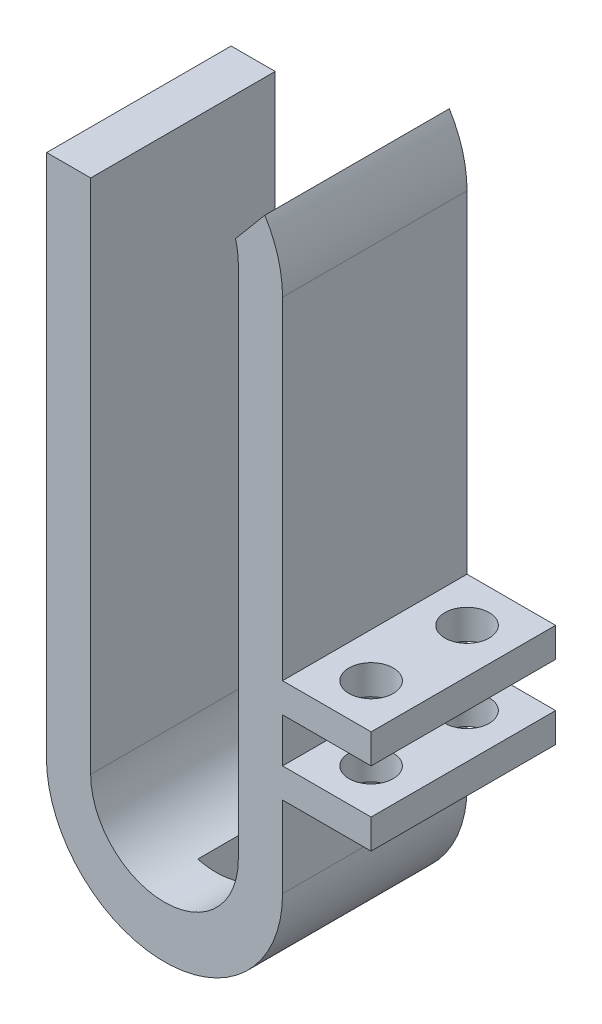
SolidWorks part; units mm, degrees
ref_plane "Front Plane" through (0, 0, 0) normal (0, 0, 1) x (1, 0, 0)
ref_plane "Top Plane" through (0, 0, 0) normal (0, 1, 0) x (1, 0, 0)
ref_plane "Right Plane" through (0, 0, 0) normal (1, 0, 0) x (0, 0, -1)
sketch "Sketch1" plane through (0, 0, 0) normal (0, 0, 1) x (1, 0, 0)
  line L0 (0, 17.5) -> (0, -17.5) construction
  line L1 (5, 17.5) -> (5, -17.5)
  line L2 (-5, 8.5) -> (-5, -17.5)
  line L3 (8, 17) -> (8, -18)
  line L4 (-8, 11.5) -> (-8, -18)
  line L6 (-8, 11.5) -> (-5, 8.5)
  line L9 (-5, 17.5) -> (-5, 8.5)
  line L10 (-8, 17) -> (-8, 11.5)
  line L11 (-6.105, 27.1604) -> (2.0351, 15.5351)
  line L12 (-5, 8.5) -> (2.0351, 15.5351)
  line L13 (-7.9844, 17.5) -> (7.9844, 17.5)
  line L14 (2.0351, 15.5351) -> (9.5686, 24.5132)
  arc A0 (5, 17.5) -> (-5, 17.5) centre (0, 17.5) ccw
  arc A1 (-5, -17.5) -> (5, -17.5) centre (0, -17.5) ccw
  arc A2 (-8, -18) -> (8, -18) centre (0, -18) ccw
  arc A3 (8, 17) -> (-8, 17) centre (0, 17) ccw
  point P2 (0, 0)
  point P15 (0, 0)
  dimension "D4" = 35
  dimension "D7" = 100
  dimension "D8" = 75
  dimension "D1" = 3
  dimension "D2" = 3
  dimension "D3" = 5
  dimension "D5" = 35
  dimension "D6" = 17
extrude "Boss-Extrude1" add sketch "Sketch1" along normal blind 12.5 contours L3 A3 A0 L1 A1 L2 L6 L4 A2 | L13 A3 L10 L6 L9 | L13 A3 L14 A0 region at (6.4922, 17.0365, 0) region at (6.4627, 18.8851, 0) region at (-6.3998, 13.6996, 0)
sketch "Sketch2" plane through (8, 0, 0) normal (1, 0, 0) x (0, 0, -1)
  line L0 (0, 17) -> (0, -18) construction
  line L7 (-12.5, 17) -> (0, 17) construction
  line L8 (-12.5, 17) -> (-12.5, -18) construction
  line L9 (-12.5, -12.5) -> (0, -12.5)
  line L10 (-12.5, -12.5) -> (-12.5, -10.5)
  line L11 (-12.5, -10.5) -> (0, -10.5)
  line L12 (0, -12.5) -> (0, -10.5)
  line L13 (-12.5, -5.5) -> (0, -5.5)
  line L14 (-12.5, -5.5) -> (-12.5, -7.5)
  line L15 (-12.5, -7.5) -> (0, -7.5)
  line L16 (0, -5.5) -> (0, -7.5)
  dimension "D1" = 22.5
  dimension "D2" = 3
  dimension "D3" = 2
  dimension "D4" = 2
extrude "Boss-Extrude2" add sketch "Sketch2" along normal blind 6
sketch "Sketch3" plane through (0, -10.5, 0) normal (0, 1, 0) x (1, 0, 0)
  line L0 (14, 0) -> (8, 0) construction
  line L1 (8, -6.25) -> (14, -6.25) construction
  line L2 (8, 0) -> (8, -12.5) construction
  line L3 (14, 0) -> (14, -12.5) construction
  circle A1 centre (11, -3) radius 1.5
  circle A2 centre (11, -9.5) radius 1.5
  point P10 (11, -9.5)
  dimension "D1" = 3
  dimension "D2" = 3
  dimension "D3" = 3
extrude "Cut-Extrude1" cut sketch "Sketch3" against normal through all both and the other way through all
sketch "Sketch5" plane through (0, 0, 0) normal (0, 1, 0) x (1, 0, 0)
  line L0 (-8, -12.5) -> (-8, 0) construction
  line L1 (-1.25, -3.5) -> (1.25, -3.5)
  line L2 (-1.25, -3.5) -> (-1.25, -9)
  line L3 (-1.25, -9) -> (1.25, -9)
  line L4 (1.25, -3.5) -> (1.25, -9)
  line L7 (5, 0) -> (-5, 0) construction
  dimension "D1" = 5.5
  dimension "D2" = 2.5
  dimension "D3" = 6.75
  dimension "D4" = 3.5
extrude "Cut-Extrude2" cut sketch "Sketch5" against normal through all
